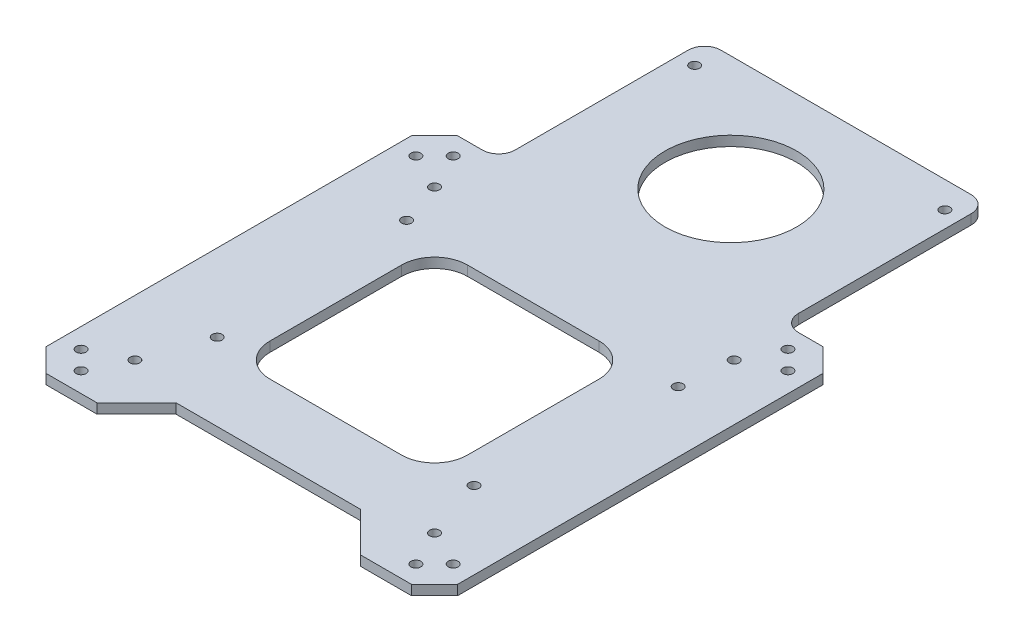
SolidWorks part; units mm, degrees
material "Thornel Mat VMA"
ref_plane "前视基准面" through (0, 0, 0) normal (0, 0, 1) x (1, 0, 0)
ref_plane "上视基准面" through (0, 0, 0) normal (0, 1, 0) x (1, 0, 0)
ref_plane "右视基准面" through (0, 0, 0) normal (1, 0, 0) x (0, 0, -1)
other "Configuration Table"
sketch "草图1" plane through (0, 0, 0) normal (0, 1, 0) x (1, 0, 0)
  line L0 (0, 0) -> (63.1315, 0) construction
  line L1 (-62.5, -62.5) -> (62.5, -62.5)
  line L2 (-62.5, -62.5) -> (-62.5, 62.5)
  line L3 (-62.5, 62.5) -> (62.5, 62.5)
  line L4 (62.5, -62.5) -> (62.5, 62.5)
  line L5 (-62.5, -62.5) -> (62.5, 62.5) construction
  line L6 (-62.5, 62.5) -> (62.5, -62.5) construction
  line L7 (0, 0) -> (0, 71.086) construction
  line L8 (50.8431, 56.5) -> (56.5, 50.8431) construction
  line L9 (43, 62.5) -> (43, 125)
  line L10 (43, 125) -> (-43, 125)
  line L11 (-43, 62.5) -> (-43, 125)
  circle A4 centre (50.8431, 56.5) radius 1.5
  circle A5 centre (56.5, 50.8431) radius 1.5
  circle A6 centre (56.5, -50.8431) radius 1.5
  circle A7 centre (50.8431, -56.5) radius 1.5
  circle A8 centre (-50.8431, -56.5) radius 1.5
  circle A9 centre (-56.5, -50.8431) radius 1.5
  circle A10 centre (-56.5, 50.8431) radius 1.5
  circle A11 centre (-50.8431, 56.5) radius 1.5
  circle A12 centre (-38, 117) radius 1.5
  circle A13 centre (38, 117) radius 1.5
  point P0 (0, 0)
  point P14 (0, 125)
  dimension "D3" = 62.5
  dimension "D5" = 3
  dimension "D6" = 3
  dimension "D7" = 3
  dimension "D8" = 8
  dimension "D13" = 76
  dimension "D1" = 125
  dimension "D2" = 125
  dimension "D4" = 86
  dimension "D9" = 45
  dimension "D10" = 6
  dimension "D11" = 6
  dimension "D12" = 117
extrude "凸台-拉伸1" add sketch "草图1" along normal blind 3 contours L1 L4 L3 L2 A10 A9 A8 A6 A5 A4 A7 A11 | L11 L3 L9 L10 region at (0, 0, 0) region at (0, 0, -93.6887)
chamfer "倒角1" distance 7 angle 45 4 edges at (-62.5, 1.5, 62.5) (-62.5, 1.5, -62.5) (62.5, 1.5, 62.5) (62.5, 1.5, -62.5)
fillet "圆角1" radius 5 4 edges at (43, 1.5, -62.5) (43, 1.5, -125) (-43, 1.5, -125) (-43, 1.5, -62.5)
sketch "草图3" plane through (0, 3, 0) normal (0, 1, 0) x (1, 0, 0)
  line L0 (0, 0) -> (95.6793, 0) construction
  line L1 (0, 0) -> (0, 105.8926) construction
  line L13 (-40, -62.5) -> (-40, -50.5)
  line L18 (-49.5, -49.5) -> (49.5, -49.5)
  line L19 (-49.5, -49.5) -> (-49.5, 49.5)
  line L20 (-49.5, 49.5) -> (49.5, 49.5)
  line L21 (49.5, -49.5) -> (49.5, 49.5)
  line L22 (-49.5, -49.5) -> (49.5, 49.5) construction
  line L23 (-49.5, 49.5) -> (49.5, -49.5) construction
  line L24 (-30, -30) -> (30, -30)
  line L25 (-30, -30) -> (-30, 30)
  line L26 (-30, 30) -> (30, 30)
  line L27 (30, -30) -> (30, 30)
  line L28 (-30, -30) -> (30, 30) construction
  line L29 (-30, 30) -> (30, -30) construction
  line L34 (-55.5, -62.5) -> (55.5, -62.5) construction
  line L35 (-40, -50.5) -> (40, -50.5)
  line L36 (0, 0) -> (0, -77.8957) construction
  line L37 (-40, -62.5) -> (40, -62.5)
  line L38 (40, -62.5) -> (40, -50.5)
  circle A4 centre (-45.5, 45.5) radius 1.5
  circle A5 centre (45.5, 45.5) radius 1.5
  circle A6 centre (45.5, -45.5) radius 1.5
  circle A7 centre (-45.5, -45.5) radius 1.5
  circle A8 centre (0, 90) radius 20
  point P30 (0, -62.5)
  point P31 (0, -50.5)
  line M36 (-55.5, -62.5) -> (55.5, -62.5)
  dimension "D3" = 3
  dimension "D7" = 40
  dimension "D8" = 90
  dimension "D1" = 99
  dimension "D2" = 99
  dimension "D4" = 4
  dimension "D5" = 60
  dimension "D6" = 60
  dimension "D9" = 80
  dimension "D10" = 12
extrude "切除-拉伸1" cut sketch "草图3" against normal blind 3 contours L24 L27 L26 L25 | A4 | A5 | A6 | A7 | A8 | L38 L35 L13 M36 region at (0, 3, 56.5) region at (0, 3, 0) region at (-45.5, 3, -45.5) region at (45.5, 3, -45.5) region at (45.5, 3, 45.5) region at (-45.5, 3, 45.5) region at (0, 3, -90)
fillet "圆角3" radius 10 4 edges at (-30, 1.5, 30) (30, 1.5, 30) (30, 1.5, -30) (-30, 1.5, -30)
chamfer "倒角2" distance 12 angle 45 2 edges at (40, 1.5, 50.5) (-40, 1.5, 50.5)
sketch "草图4" plane through (0, 3, 0) normal (0, 1, 0) x (1, 0, 0)
  line L0 (0, 0) -> (147.6965, 0) construction
  line L1 (0, 0) -> (0, 135.7677) construction
  line L2 (-50, 45) -> (70.2761, 45) construction
  line L7 (-50, 45) -> (-50, -77.0358) construction
  circle A0 centre (-41, 32.5) radius 1.5
  circle A1 centre (44, 30) radius 1.5
  circle A2 centre (-39, -27) radius 1.5
  circle A3 centre (39, -27) radius 1.5
  dimension "D1" = 3
  dimension "D3" = 12.5
  dimension "D5" = 3
  dimension "D8" = 3
  dimension "D10" = 3
  dimension "D12" = 72
  dimension "D2" = 9
  dimension "D4" = 94
  dimension "D6" = 15
  dimension "D7" = 11
  dimension "D9" = 72
  dimension "D11" = 89
  dimension "D13" = 50
  dimension "D14" = 45
extrude "切除-拉伸2" cut sketch "草图4" against normal blind 10
